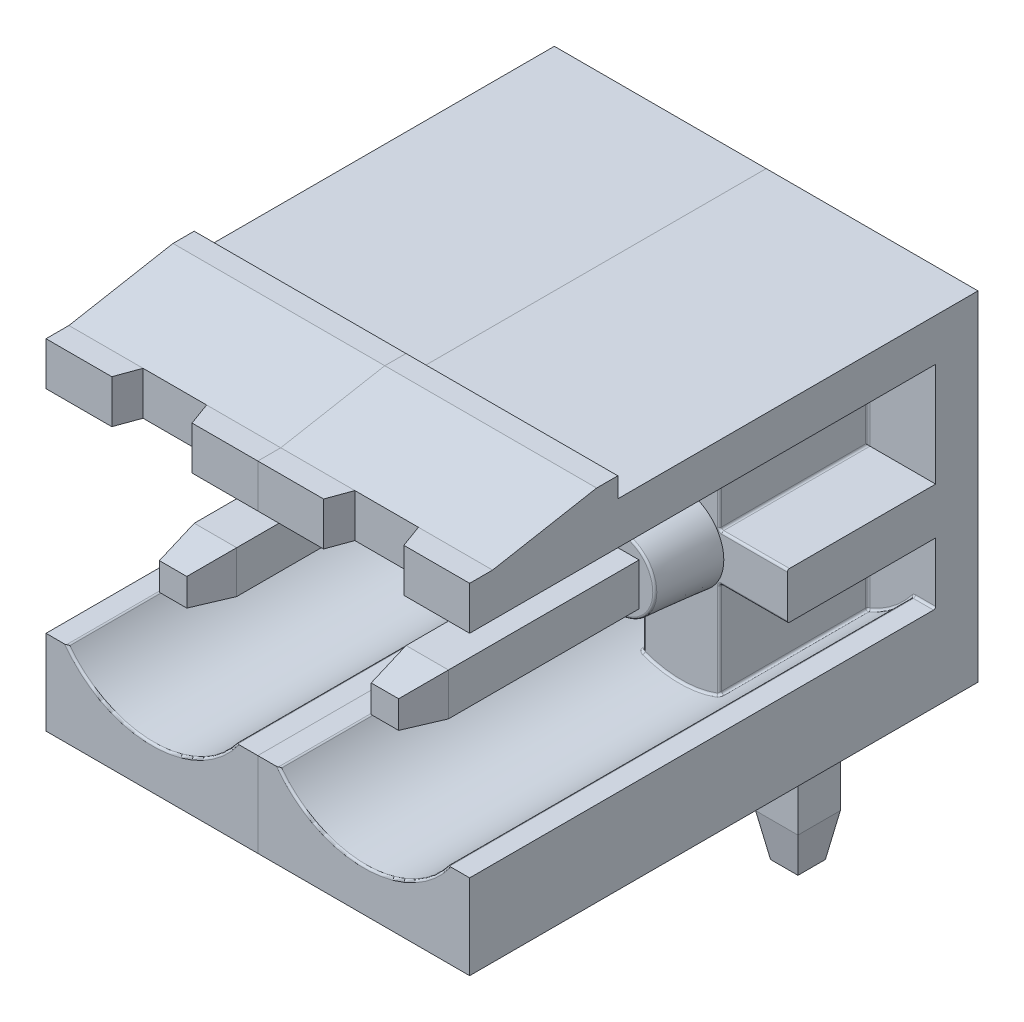
SolidWorks part; units mm, degrees
ref_plane "Спереди" through (0, 0, 0) normal (0, 0, 1) x (1, 0, 0)
ref_plane "Сверху" through (0, 0, 0) normal (0, 1, 0) x (1, 0, 0)
ref_plane "Справа" through (0, 0, 0) normal (1, 0, 0) x (0, 0, -1)
sketch "Эскиз1" plane through (0, 0, 0) normal (0, 0, 1) x (1, 0, 0)
  line L1 (-2.5, 0) -> (2.5, 0)
  line L2 (-2.5, 0) -> (-2.5, 8)
  line L3 (-2.5, 8) -> (2.5, 8)
  line L4 (2.5, 0) -> (2.5, 8)
extrude "Вытянуть1" add sketch "Эскиз1" along normal blind 12
sketch "Эскиз2" plane through (0, 0, 12) normal (0, 0, 1) x (1, 0, 0)
  line L0 (-2.5, 8) -> (-2.5, 0) construction
  line L1 (-2.5, 7) -> (2.5, 7)
  line L2 (-2.5, 7) -> (-2.5, 2)
  line L3 (-2.5, 2) -> (2.5, 2)
  line L4 (2.5, 7) -> (2.5, 2)
  line L5 (2.5, 0) -> (2.5, 8) construction
  dimension "D1" = 1
  dimension "D2" = 2
extrude "Вытянуть2" cut sketch "Эскиз2" against normal blind 11
sketch "Эскиз5" plane through (0, 0, 12) normal (0, 0, 1) x (1, 0, 0)
  line L0 (-2.5, 2) -> (-2, 2) construction
  line L1 (-2.5, 2) -> (2.5, 2) construction
  line L2 (2.5, 2) -> (2, 2) construction
  line L3 (0, 0) -> (0, 1) construction
  line L4 (-2.5, 0) -> (2.5, 0) construction
  circle A0 centre (0, 3.5) radius 2.5
extrude "Вытянуть3" cut sketch "Эскиз5" against normal blind 11
sketch "Эскиз6" plane through (0, 0, 12) normal (0, 0, 1) x (1, 0, 0)
  line L1 (0.5, 4.5) -> (-0.5, 4.5)
  line L2 (0.5, 4.5) -> (0.5, 3.5)
  line L3 (0.5, 3.5) -> (-0.5, 3.5)
  line L4 (-0.5, 4.5) -> (-0.5, 3.5)
  line L5 (0.5, 4.5) -> (-0.5, 3.5) construction
  line L6 (0.5, 3.5) -> (-0.5, 4.5) construction
  point P0 (0, 4)
  dimension "D1" = 1
  dimension "D2" = 1
sketch "Эскиз9" plane through (0, 0, 0) normal (0, -1, 0) x (1, 0, 0)
  line L0 (-2.5, 1.75) -> (2.5, 1.75) construction
  line L1 (-2.5, 12) -> (-2.5, 0) construction
  line L2 (2.5, 12) -> (2.5, 0) construction
  line L4 (-0.5, 2.25) -> (0.5, 2.25)
  line L5 (-0.5, 2.25) -> (-0.5, 1.25)
  line L6 (-0.5, 1.25) -> (0.5, 1.25)
  line L7 (0.5, 2.25) -> (0.5, 1.25)
  line L8 (-0.5, 2.25) -> (0.5, 1.25) construction
  line L9 (-0.5, 1.25) -> (0.5, 2.25) construction
  point P2 (0, 1.75)
  dimension "D1" = 1.75
sketch "Эскиз13" plane through (0, 0, 1) normal (0, 0, 1) x (1, 0, 0)
  line L0 (2.5, 7) -> (-2.5, 7) construction
  line L1 (-0.9, 1) -> (0.9, 1)
  line L2 (-0.9, 1) -> (-0.9, 7)
  line L3 (-0.9, 7) -> (0.9, 7)
  line L4 (0.9, 1) -> (0.9, 7)
  line L5 (-0.9, 1) -> (0.9, 7) construction
  line L6 (-0.9, 7) -> (0.9, 1) construction
  line L7 (2.5, 2) -> (2.5, 7) construction
  line L8 (-2.5, 4.55) -> (2.5, 4.55)
  line L9 (-2.5, 4.55) -> (-2.5, 3.45)
  line L10 (-2.5, 3.45) -> (2.5, 3.45)
  line L11 (2.5, 4.55) -> (2.5, 3.45)
  line L12 (-2.5, 4.55) -> (2.5, 3.45) construction
  line L13 (-2.5, 3.45) -> (2.5, 4.55) construction
  point P0 (0, 4)
  point P7 (0, 4)
  line M1 (2.5, 2) -> (2.5, 7)
  line M2 (2.5, 7) -> (-2.5, 7)
  line M3 (-2.5, 7) -> (-2.5, 2)
  arc M5 (-2, 2) -> (2, 2) centre (0, 3.5) ccw
  dimension "D1" = 1.1
  dimension "D2" = 1.8
extrude "Вытянуть13" add sketch "Эскиз13" along normal blind 3.5 contours L2 L10 L4 L8 | L2 L8 L4 M2 | L10 L2 L8 M3 | L10 L2 L4 M5 | L4 L10 L8 M1 region at (0, 2.252, 1) region at (-1.7, 4, 1) region at (0, 4, 1) region at (1.7, 4, 1) region at (0, 5.775, 1)
sketch "Эскиз14" plane through (0, 0, 4.5) normal (0, 0, 1) x (1, 0, 0)
  circle A0 centre (0, 4) radius 1
extrude "Вытянуть14" add sketch "Эскиз14" along normal blind 1.5
chamfer "Фаска1" distance 1.5 angle 5 1 edges at (1, 4, 6) first distance on face at (1, 4, 6)
sketch "Эскиз15" plane through (2.5, 0, 0) normal (1, 0, 0) x (0, 0, -1)
  line L0 (-12, 8) -> (-8.5024, 8)
  line L1 (-12, 8) -> (0, 8) construction
  line L2 (-8.5024, 8) -> (-8.5024, 8.4712)
  line L3 (-8.5024, 8.4712) -> (-9.0026, 8.4712)
  line L4 (-9.0026, 8.4712) -> (-11.4588, 8.0219)
  line L5 (-11.4588, 8.0219) -> (-12, 8.0219)
  line L6 (-12, 8.0219) -> (-12, 8)
extrude "Вытянуть15" add sketch "Эскиз15" against normal blind 5
sketch "Эскиз16" plane through (0, 8.0219, 0) normal (0, 1, 0) x (1, 0, 0)
  line L0 (0.75, -11.4588) -> (-0.75, -11.4588)
  line L1 (-2.5, -11.4588) -> (2.5, -11.4588) construction
  line L2 (-0.75, -11.4588) -> (-0.947, -12)
  line L3 (-2.5, -12) -> (2.5, -12) construction
  line L4 (0.75, -11.4588) -> (0.947, -12)
  line L5 (0.947, -12) -> (-0.947, -12)
  dimension "D1" = 1.75
  dimension "D2" = 1.75
extrude "Вытянуть16" cut sketch "Эскиз16" against normal up to next
sketch "Эскиз17" plane through (0, 0, 0) normal (0, 0, -1) x (-1, 0, 0)
  line L0 (2.5, 0) -> (-2.5, 0) construction
  line L1 (-0.6, 0) -> (0.6, 0)
  line L2 (-0.6, 0) -> (-0.6, 5)
  line L3 (-0.6, 5) -> (0.6, 5)
  line L4 (0.6, 0) -> (0.6, 5)
  dimension "D1" = 3
  dimension "D2" = 1.2
  dimension "D3" = 1.9
extrude "Вытянуть17" cut sketch "Эскиз17" against normal blind 2.25
sketch "Эскиз18" plane through (0, 0, 0) normal (0, 0, -1) x (-1, 0, 0)
  line L0 (-0.6, 0) -> (-2.5, 0) construction
  line L1 (-1.75, 0) -> (1.75, 0)
  line L2 (-1.75, 0) -> (-1.75, 6)
  line L3 (-1.75, 6) -> (1.75, 6)
  line L4 (1.75, 0) -> (1.75, 6)
  dimension "D1" = 0.75
  dimension "D2" = 3.5
  dimension "D3" = 2
extrude "Вытянуть18" cut sketch "Эскиз18" against normal blind 0.1
extrude "Вытянуть19" add sketch "Эскиз6" against normal up to body separate body
sketch "Эскиз19" plane through (0, 0, 12) normal (0, 0, 1) x (1, 0, 0)
  line L1 (-0.5, 4.5) -> (0.5, 4.5)
  line L2 (-0.5, 4.5) -> (-0.5, 3.5)
  line L3 (-0.5, 3.5) -> (0.5, 3.5)
  line L4 (0.5, 4.5) -> (0.5, 3.5)
extrude "Вытянуть20" cut sketch "Эскиз19" against normal blind 0.5
extrude "Вытянуть22" add sketch "Эскиз9" against normal up to body and the other way blind 4 separate body
chamfer "Фаска2" distance 1 angle 10 4 edges at (0, 4.5, 11.5) (0.5, 4, 11.5) (0, 3.5, 11.5) (-0.5, 4, 11.5) first distance on face at (0, 4.5, 8.75) first distance on face at (0.5, 4, 8.75) first distance on face at (0, 3.5, 8.75) first distance on face at (-0.5, 4, 8.75)
chamfer "Фаска3" distance 1 angle 10 4 edges at (0, -4, 1.25) (-0.5, -4, 1.75) (0, -4, 2.25) (0.5, -4, 1.75) first distance on face at (0, 0.5, 1.25) first distance on face at (-0.5, 0.5, 1.75) first distance on face at (0, 0.5, 2.25) first distance on face at (0.5, 0.5, 1.75)
fillet "Скругление3" radius 0.05 30 edges at (1.7, 3.45, 4.5) (1.7, 4.55, 4.5) (0, 7, 4.5) (-1.7, 4.55, 4.5) (-1.7, 3.45, 4.5) (2.25, 2, 1) (-2.25, 2, 1) (0.8688, 4, 6) (0.9, 2.3088, 4.5) (0.9, 3.45, 2.75) (0.9, 2.3088, 1) (0.9, 4.55, 2.75) (0.9, 5.775, 4.5) (0.9, 7, 2.75) (0.9, 5.775, 1) (-0.9, 7, 2.75) (-0.9, 5.775, 4.5) (-0.9, 4.55, 2.75) (-0.9, 5.775, 1) (-0.9, 3.45, 2.75) (-0.9, 2.3088, 4.5) (-0.9, 2.3088, 1) (0.9, 1.1676, 2.75) (1.5085, 1.5064, 1) (2, 2, 6.5) (0, 1, 12) (-2, 2, 6.5) (-1.5085, 1.5064, 1) (-0.9, 1.1676, 2.75) (0, 1, 4.5)
pattern_linear "Линейный массив1" count 2 spacing 5 along (1, 0, 0) of bodies 118 116 114
